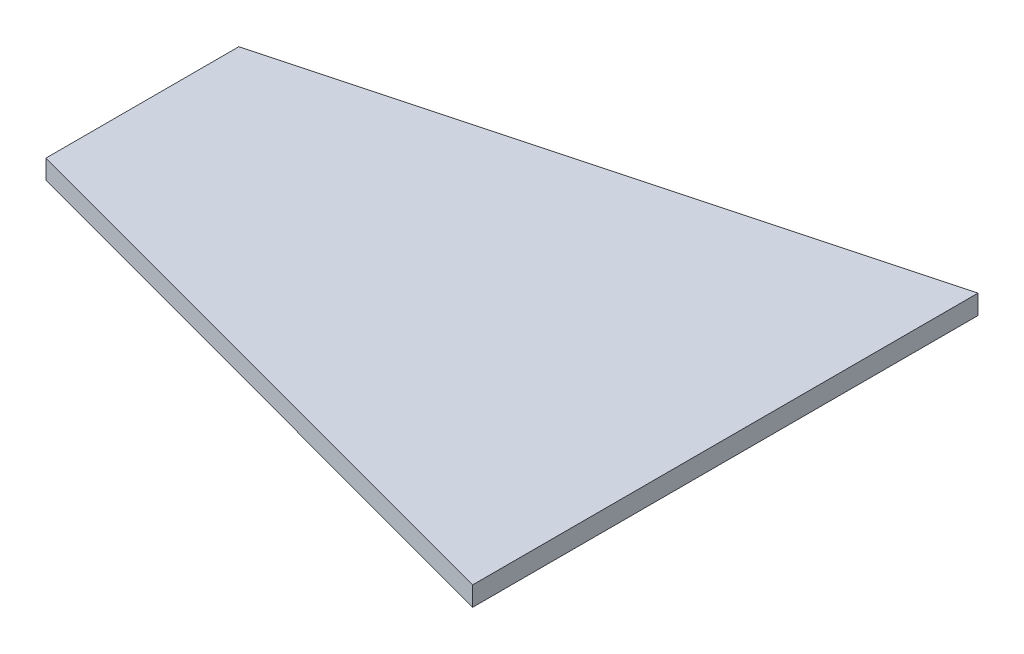
SolidWorks part; units mm, degrees
ref_plane "Front Plane" through (0, 0, 0) normal (0, 0, 1) x (1, 0, 0)
ref_plane "Top Plane" through (0, 0, 0) normal (0, 1, 0) x (1, 0, 0)
ref_plane "Right Plane" through (0, 0, 0) normal (1, 0, 0) x (0, 0, -1)
sketch "Sketch1" plane through (0, 0, 0) normal (0, 1, 0) x (1, 0, 0)
  line L0 (0, 0) -> (0, 82.55)
  line L1 (0, 82.55) -> (-95.25, 57.023)
  line L2 (-95.25, 57.023) -> (-95.25, 25.527)
  line L3 (-95.25, 25.527) -> (0, 0)
  dimension "D1" = 31.496
  dimension "D2" = 95.25
  dimension "D3" = 82.55
extrude "Boss-Extrude1" add sketch "Sketch1" along normal blind 3.175
